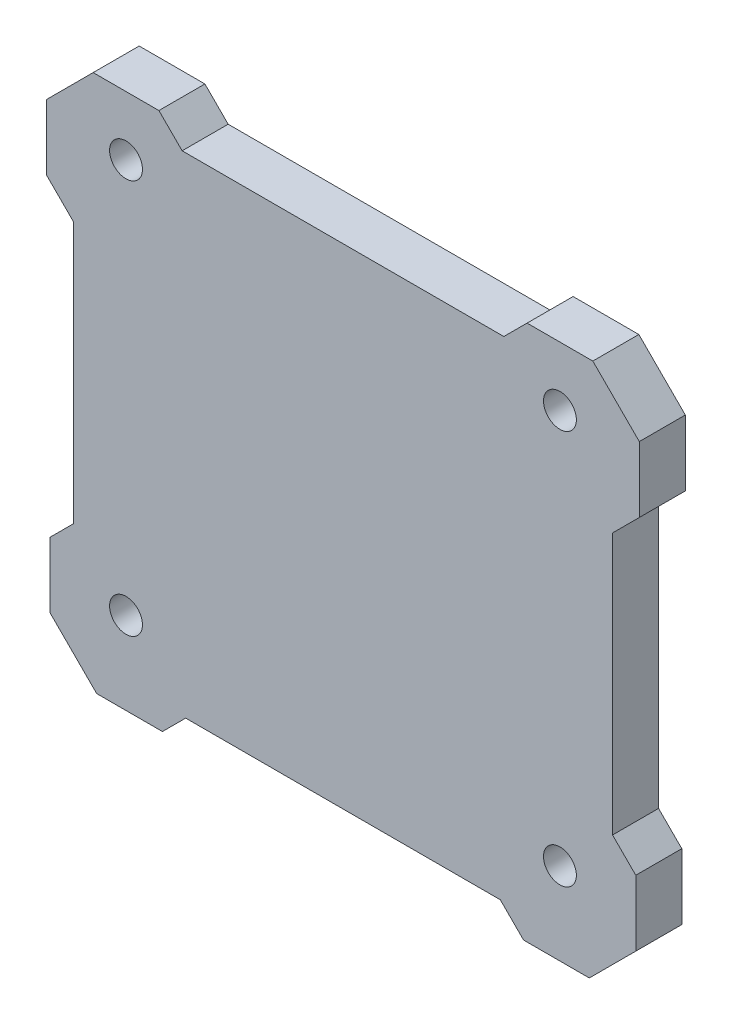
SolidWorks part; units mm, degrees
ref_plane "Alzado" through (0, 0, 0) normal (0, 0, 1) x (1, 0, 0)
ref_plane "Planta" through (0, 0, 0) normal (0, 1, 0) x (1, 0, 0)
ref_plane "Vista lateral" through (0, 0, 0) normal (1, 0, 0) x (0, 0, -1)
sketch "Croquis1" plane through (0, 0, 0) normal (0, 0, 1) x (1, 0, 0)
  line L0 (0, 0) -> (0, 36.5) construction
  line L5 (33, 30) -> (-33, 30)
  line L10 (33, 30) -> (33, -30)
  line L11 (33, -30) -> (-33, -30)
  line L12 (-33, 30) -> (-33, -30)
  line L13 (33, 30) -> (-33, -30) construction
  line L14 (33, -30) -> (-33, 30) construction
  line L15 (-41, 39) -> (41, 39)
  line L16 (-41, 39) -> (-41, -39)
  line L17 (-41, -39) -> (41, -39)
  line L18 (41, 39) -> (41, -39)
  line L19 (-41, 39) -> (41, -39) construction
  line L20 (-41, -39) -> (41, 39) construction
  circle A0 centre (-33, 30) radius 2.5
  circle A1 centre (33, 30) radius 2.5
  circle A2 centre (33, -30) radius 2.5
  circle A3 centre (-33, -30) radius 2.5
  point P0 (0, 0)
  point P5 (0, 0)
  dimension "D5" = 36.5
  dimension "D1" = 66
  dimension "D2" = 60
  dimension "D3" = 78
  dimension "D4" = 82
extrude "Saliente-Extruir5" add sketch "Croquis1" along normal blind 7 contours L15 | A3 L11 A2 L10 A1 L5 A0 L12 | L18 L15 L16 L17 A3 L12 A0 L5 A1 L10 A2 L11 region at (0, 0, 0) region at (0, 37.8683, 0)
sketch "Croquis6" plane through (0, 0, 7) normal (0, 0, 1) x (1, 0, 0)
  line L2 (-41, 39) -> (0, 39) construction
  line L3 (-38, 39) -> (38, 39)
  line L4 (-41, 39) -> (41, 39) construction
  line L5 (38, 39) -> (45.0711, 31.9289)
  line L6 (38, 39) -> (38, -39) construction
  line L7 (-41, -39) -> (41, -39) construction
  line L8 (45.0711, 31.9289) -> (45.0711, 21.9289)
  line L9 (45.0711, 21.9289) -> (41, 17.8579)
  line L10 (41, -39) -> (44.5355, -35.4645)
  line L11 (41, 39) -> (41, -39) construction
  line L12 (44.5355, -35.4645) -> (44.5355, -25.4645)
  line L13 (45.0711, 21.9289) -> (41, 21.9289) construction
  line L16 (44.5355, -25.4645) -> (41, -21.9289)
  line L17 (44.5355, -35.4645) -> (37.4645, -42.5355)
  line L18 (37.4645, -42.5355) -> (27.4645, -42.5355)
  line L19 (27.4645, -42.5355) -> (23.9289, -39)
  line L20 (-45.0711, 21.9289) -> (-41, 21.9289) construction
  line L21 (-38, 39) -> (-38, -39) construction
  line L22 (-27.4645, -42.5355) -> (-23.9289, -39)
  line L23 (-37.4645, -42.5355) -> (-27.4645, -42.5355)
  line L24 (-44.5355, -35.4645) -> (-37.4645, -42.5355)
  line L25 (-44.5355, -25.4645) -> (-41, -21.9289)
  line L27 (-44.5355, -35.4645) -> (-44.5355, -25.4645)
  line L28 (-41, -39) -> (-44.5355, -35.4645)
  line L29 (-45.0711, 21.9289) -> (-41, 17.8579)
  line L30 (-45.0711, 31.9289) -> (-45.0711, 21.9289)
  line L31 (-38, 39) -> (-45.0711, 31.9289)
  line M22 (41, 39) -> (-41, 39)
  line M23 (-41, 39) -> (-41, -39)
  line M24 (-41, -39) -> (41, -39)
  line M25 (41, -39) -> (41, 39)
  dimension "D2" = 10
  dimension "D3" = 10
  dimension "D4" = 45
  dimension "D5" = 45
  dimension "D8" = 45
  dimension "D9" = 45
  dimension "D10" = 10
  dimension "D11" = 45
extrude "Saliente-Extruir7" add sketch "Croquis6" against normal through all contours L31 L30 L29 M23 | M22 | L3 | L9 L8 L5 M25 | L12 L16 L10 M25 | L19 L18 L17 M24 | L27 L24 L25 M23 | L24 L23 L22 M24 region at (-42.8392, 26.9289, 7) region at (42.8392, 26.9289, 7) region at (-42.6139, -30.4645, 7) region at (42.6139, -30.4645, 7) region at (-32.4645, -40.6139, 7) region at (32.4645, -40.6139, 7)
sketch "Croquis7" plane through (0, 0, 7) normal (0, 0, 1) x (1, 0, 0)
  line L0 (-45.0711, 31.9289) -> (-38, 39)
  line L1 (-41, 39) -> (41, 39) construction
  line L2 (-38, 39) -> (-28, 39)
  line L3 (-28, 39) -> (-24.4645, 35.4645)
  line L4 (24.4645, 35.4645) -> (-24.4645, 35.4645)
  line L5 (45.0711, 31.9289) -> (38, 39)
  line L6 (38, 39) -> (28, 39)
  line L7 (28, 39) -> (24.4645, 35.4645)
  line L8 (41, 36) -> (41, 39)
  line L9 (41, 39) -> (-41, 39)
  line L10 (-41, 39) -> (-41, 36)
  line L11 (-41, 39) -> (-41, 36) construction
extrude "Cortar-Extruir-Lámina1" cut sketch "Croquis7" against normal through all thin thin type one direction wall 10
